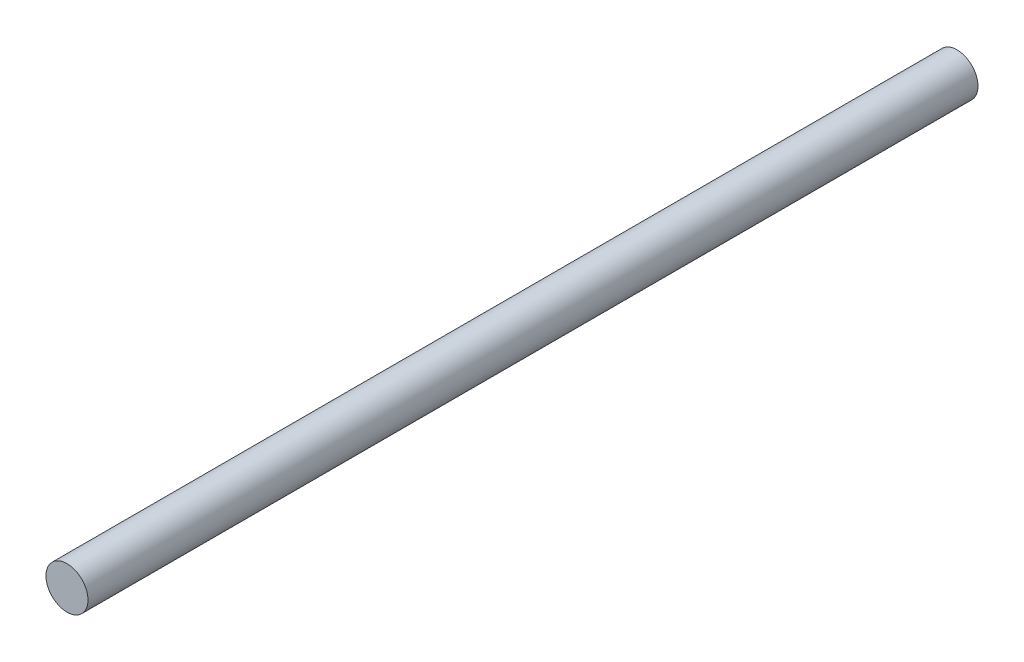
SolidWorks part; units mm, degrees
material "6061-T6 (SS)"
ref_plane "Front Plane" through (0, 0, 0) normal (0, 0, 1) x (1, 0, 0)
ref_plane "Top Plane" through (0, 0, 0) normal (0, 1, 0) x (1, 0, 0)
ref_plane "Right Plane" through (0, 0, 0) normal (1, 0, 0) x (0, 0, -1)
sketch "Sketch1" plane through (0, 0, 0) normal (0, 0, 1) x (1, 0, 0)
  circle A0 centre (0, 0) radius 2.4892
  dimension "D1" = 4.9784
extrude "Boss-Extrude1" add sketch "Sketch1" along normal blind 105.41
